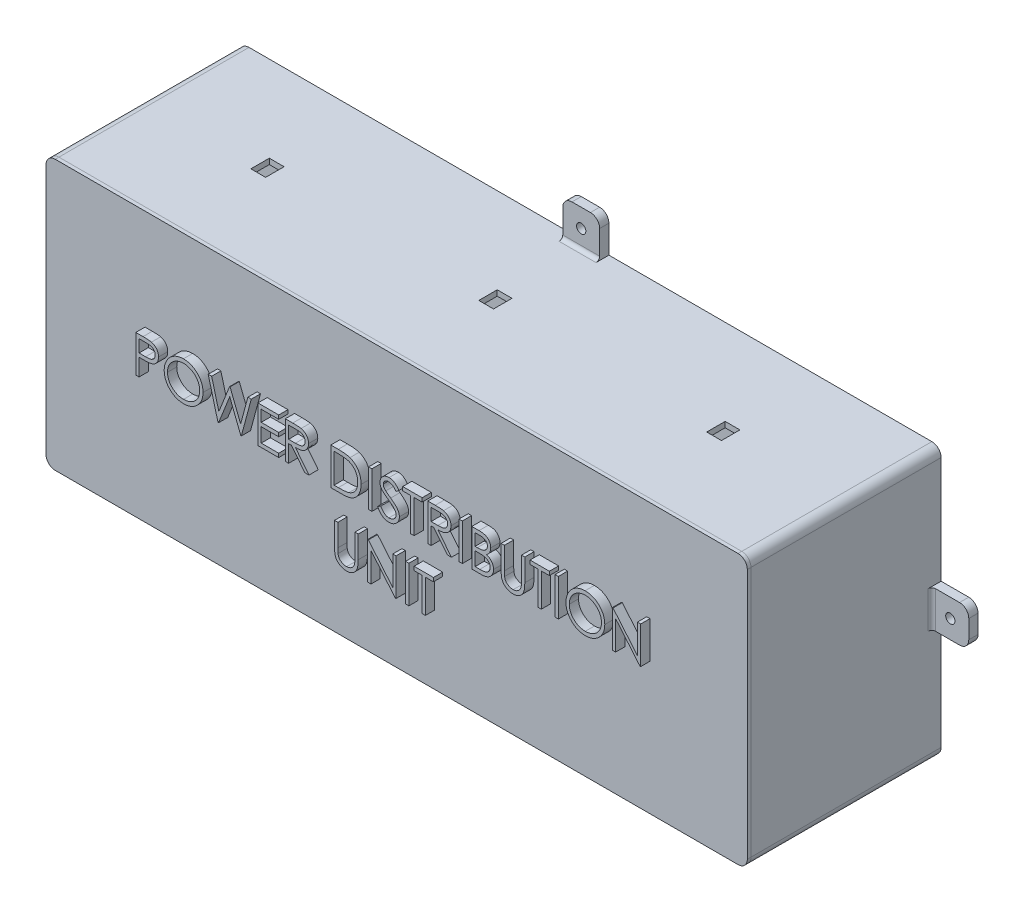
SolidWorks part; units mm, degrees
ref_plane "Front Plane" through (0, 0, 0) normal (0, 0, 1) x (1, 0, 0)
ref_plane "Top Plane" through (0, 0, 0) normal (0, 1, 0) x (1, 0, 0)
ref_plane "Right Plane" through (0, 0, 0) normal (1, 0, 0) x (0, 0, -1)
sketch "Sketch1" plane through (0, 0, 0) normal (0, 0, 1) x (1, 0, 0)
  line L0 (-190, 73) -> (190, 73)
  line L1 (-187, -70) -> (187, -70)
  line L2 (-187, -70) -> (-187, 70)
  line L3 (-187, 70) -> (187, 70)
  line L4 (187, -70) -> (187, 70)
  line L5 (0, 70) -> (0, -70) construction
  line L6 (-187, 0) -> (187, 0) construction
  line L7 (190, -73) -> (190, 73)
  line L8 (-190, -73) -> (190, -73)
  line L9 (-190, -73) -> (-190, 73)
  point P0 (0, 0)
  dimension "D1" = 140
  dimension "D2" = 380
  dimension "D3" = 3
extrude "Boss-Extrude1" add sketch "Sketch1" along normal blind 100
sketch "Sketch2" plane through (0, 0, 0) normal (0, 0, -1) x (-1, 0, 0)
  line L0 (-190, -73) -> (-190, 73) construction
  line L1 (190, -73) -> (-190, -73) construction
  line L2 (190, 73) -> (190, -73) construction
  line L3 (-190, 73) -> (190, 73) construction
  line L4 (-190, -73) -> (-190, 73)
  line L5 (190, -73) -> (-190, -73)
  line L6 (190, 73) -> (190, -73)
  line L7 (-190, 73) -> (190, 73)
extrude "Boss-Extrude2" add sketch "Sketch2" along normal blind 3
ref_plane "Plane1" through (0, 0, 5) normal (0, 0, 1) x (1, 0, 0)
sketch "Sketch3" plane through (0, 0, 5) normal (0, 0, 1) x (1, 0, 0)
  line L0 (-177, 60) -> (-177, -60)
  line L1 (-177, -60) -> (177, -60)
  line L2 (177, -60) -> (177, 60)
  line L3 (177, 60) -> (-177, 60)
  line L4 (-187, 70) -> (-187, -70)
  line L5 (-187, -70) -> (187, -70)
  line L6 (187, -70) -> (187, 70)
  line L7 (187, 70) -> (-187, 70)
  line L8 (-187, 70) -> (-187, -70)
  line L9 (-187, -70) -> (187, -70)
  line L10 (187, -70) -> (187, 70)
  line L11 (187, 70) -> (-187, 70)
  dimension "D1" = 0
  dimension "D2" = 10
extrude "Boss-Extrude3" add sketch "Sketch3" along normal blind 3 separate body contours L2 L3 L0 L1 region at (0, 0, 5)
sketch "Sketch4" plane through (0, 70, 0) normal (0, -1, 0) x (1, 0, 0)
  line L1 (190, 48.5) -> (-190, 48.5) construction
  line L2 (190, 100) -> (190, -3) construction
  line L3 (-190, 100) -> (-190, -3) construction
  line L15 (127.5, 43.5) -> (119.5, 43.5)
  line L16 (127.5, 43.5) -> (127.5, 53.5)
  line L21 (127.5, 53.5) -> (119.5, 53.5)
  line L22 (119.5, 43.5) -> (119.5, 53.5)
  line L27 (123.5, 53.5) -> (123.5, 43.5) construction
  line L28 (127.5, 48.5) -> (119.5, 48.5) construction
  line L30 (-127.5, 43.5) -> (-119.5, 43.5)
  line L31 (-127.5, 43.5) -> (-127.5, 53.5)
  line L32 (-127.5, 53.5) -> (-119.5, 53.5)
  line L33 (-119.5, 43.5) -> (-119.5, 53.5)
  line L34 (-123.5, 53.5) -> (-123.5, 43.5) construction
  line L35 (-127.5, 48.5) -> (-119.5, 48.5) construction
  line L36 (4, 43.5) -> (-4, 43.5)
  line L37 (4, 43.5) -> (4, 53.5)
  line L38 (4, 53.5) -> (-4, 53.5)
  line L39 (-4, 43.5) -> (-4, 53.5)
  line L40 (0, 53.5) -> (0, 43.5) construction
  line L41 (4, 48.5) -> (-4, 48.5) construction
  point P6 (123.5, 48.5)
  point P7 (-123.5, 48.5)
  point P8 (123.5, 48.5)
  point P12 (-123.5, 48.5)
  point P16 (0, 48.5)
  point P17 (0, 48.5)
  dimension "D5" = 8
  dimension "D6" = 10
  dimension "D7" = 10
  dimension "D1" = 380
  dimension "D2" = 66.5
  dimension "D3" = 66.5
  dimension "D4" = 190
  dimension "D8" = 8
  dimension "D9" = 8
  dimension "D10" = 10
extrude "Cut-Extrude1" cut sketch "Sketch4" against normal up to surface (3 mm away) contours L22 L15 L16 L21 | L39 L36 L37 L38 | L31 L32 L33 L30 region at (123.5, 70, 48.5) region at (0, 70, 48.5) up to face at (0, 73, 48.5)
sketch "Sketch6" plane through (-190, 0, 0) normal (-1, 0, 0) x (0, 0, 1)
  line L0 (48.5, 73) -> (48.5, -73) construction
  line L5 (100, 73) -> (100, -73) construction
  line L6 (43.5, -28.6) -> (53.5, -28.6)
  line L7 (43.5, -33.8) -> (53.5, -33.8)
  line L8 (43.5, -33.8) -> (43.5, -41.8)
  line L9 (43.5, -41.8) -> (53.5, -41.8)
  line L10 (53.5, -33.8) -> (53.5, -41.8)
  line L11 (48.5, -41.8) -> (48.5, -33.8) construction
  line L12 (43.5, -37.8) -> (53.5, -37.8) construction
  line L17 (43.5, -28.6) -> (43.5, -36.6)
  line L18 (56, 2.6) -> (41, 2.6) construction
  line L19 (56, 37.8) -> (41, 37.8) construction
  line L20 (48.5, 45.3) -> (48.5, 30.3) construction
  line L21 (43.5, -36.6) -> (53.5, -36.6)
  line L22 (-3, -73) -> (-3, 73) construction
  line L23 (100, 73) -> (-3, 73) construction
  line L24 (53.5, -28.6) -> (53.5, -36.6)
  line L25 (100, -73) -> (-3, -73) construction
  line L26 (48.5, -36.6) -> (48.5, -28.6) construction
  line L30 (43.5, -32.6) -> (53.5, -32.6) construction
  circle A0 centre (48.5, 37.8) radius 7.5
  circle A1 centre (48.5, 2.6) radius 7.5
  point P2 (48.5, -32.6)
  point P6 (48.5, -37.8)
  point P12 (48.5, 2.6)
  dimension "D8" = 15
  dimension "D6" = 15
  dimension "D1" = 35.2
  dimension "D2" = 8
  dimension "D3" = 10
  dimension "D4" = 35.2
  dimension "D5" = 10
  dimension "D7" = 35.2
  dimension "D9" = 35.2
  dimension "D10" = 8
  dimension "D11" = 51.5
  dimension "D12" = 51.5
extrude "Cut-Extrude2" cut sketch "Sketch6" against normal up to surface (3 mm away) contours A1 | L8 L21 L10 L7 | L24 L6 L17 L7 | A0 region at (-190, -31.2, 48.5) region at (-190, -35.2, 48.5) region at (-190, 37.8, 48.5) region at (-190, 2.6, 48.5) up to face at (-187, 0, 50)
sketch "Sketch7" plane through (0, -73, 0) normal (0, -1, 0) x (1, 0, 0)
  line L0 (0, 22) -> (0, 12) construction
  line L1 (-5, 17) -> (5, 17) construction
  line L4 (190, -3) -> (-190, -3) construction
  circle A0 centre (0, 17) radius 5
  dimension "D2" = 10
  dimension "D3" = 0
  dimension "D5" = 20
extrude "Cut-Extrude3" cut sketch "Sketch7" against normal up to surface (3 mm away) up to face at (0, -70, 50)
fillet "Fillet1" radius 5 4 edges at (190, 73, 48.5) (190, -73, 48.5) (-190, 73, 48.5) (-190, -73, 48.5)
fillet "Fillet2" radius 5 4 edges at (187, 70, 50) (-187, 70, 50) (187, -70, 50) (-187, -70, 50)
sketch "Sketch8" plane through (-187, 0, 0) normal (1, 0, 0) x (0, 0, -1)
  line L0 (0, 65) -> (-100, 65) construction
  line L1 (-97, -22.5) -> (-94, -22.5)
  line L2 (-97, -22.5) -> (-97, -7.5)
  line L3 (-97, -7.5) -> (-94, -7.5)
  line L4 (-94, -22.5) -> (-94, -7.5)
  line L5 (-95.5, -7.5) -> (-95.5, -22.5) construction
  line L6 (-97, -15) -> (-94, -15) construction
  line L7 (-100, 65) -> (-100, -65) construction
  line L8 (-100, -65) -> (0, -65) construction
  point P0 (-95.5, -15)
  dimension "D1" = 3
  dimension "D2" = 15
  dimension "D3" = 80
  dimension "D4" = 3
  dimension "D5" = 50
extrude "Boss-Extrude4" add sketch "Sketch8" along normal blind 15
sketch "Sketch9" plane through (0, 70, 0) normal (0, -1, 0) x (1, 0, 0)
  line L0 (182, 0) -> (182, 100) construction
  line L1 (74.5, 94) -> (89.5, 94)
  line L2 (74.5, 94) -> (74.5, 97)
  line L3 (74.5, 97) -> (89.5, 97)
  line L4 (89.5, 94) -> (89.5, 97)
  line L5 (82, 97) -> (82, 94) construction
  line L6 (74.5, 95.5) -> (89.5, 95.5) construction
  line L7 (182, 100) -> (-182, 100) construction
  line L8 (-182, 100) -> (-182, 0) construction
  line L9 (-89.5, 94) -> (-74.5, 94)
  line L10 (-89.5, 94) -> (-89.5, 97)
  line L11 (-89.5, 97) -> (-74.5, 97)
  line L12 (-74.5, 94) -> (-74.5, 97)
  line L13 (-82, 97) -> (-82, 94) construction
  line L14 (-89.5, 95.5) -> (-74.5, 95.5) construction
  point P0 (82, 95.5)
  point P8 (-82, 95.5)
  dimension "D1" = 15
  dimension "D2" = 3
  dimension "D3" = 100
  dimension "D4" = 3
  dimension "D5" = 100
  dimension "D6" = 3
  dimension "D7" = 3
  dimension "D8" = 164
  dimension "D9" = 15
extrude "Boss-Extrude5" add sketch "Sketch9" along normal blind 15
ref_plane "Plane2" through (0, 0, 0) normal (0, -1, 0) x (-1, 0, 0)
ref_plane "Plane3" through (0, 0, 0) normal (1, 0, 0) x (0, 0, -1)
mirror "Mirror1" about plane through (0, 0, 0) normal (1, 0, 0) of "Boss-Extrude4"
mirror "Mirror2" about plane through (0, 0, 0) normal (0, -1, 0) of "Boss-Extrude5"
fillet "Fillet3" radius 3 12 edges at (89.5, -55, 95.5) (74.5, -55, 95.5) (172, -7.5, 95.5) (172, -22.5, 95.5) (74.5, 55, 95.5) (89.5, 55, 95.5) (-172, -7.5, 95.5) (-172, -22.5, 95.5) (-74.5, -55, 95.5) (-89.5, -55, 95.5) (-74.5, 55, 95.5) (-89.5, 55, 95.5)
sketch "Sketch10" plane through (0, 0, -3) normal (0, 0, -1) x (-1, 0, 0)
  line L0 (-185, 73) -> (185, 73) construction
  line L1 (-10, 73) -> (10, 73)
  line L2 (-10, 73) -> (-10, 88)
  line L3 (-5, 93) -> (5, 93)
  line L4 (10, 73) -> (10, 88)
  line L5 (-2.5, 83) -> (2.5, 83) construction
  line L6 (0, 85.5) -> (0, 80.5) construction
  line L7 (0, 80.5) -> (0, 0) construction
  circle A0 centre (0, 83) radius 2.5
  arc A1 (5, 93) -> (10, 88) centre (5, 88) cw
  arc A2 (-10, 88) -> (-5, 93) centre (-5, 88) cw
  dimension "D1" = 5
  dimension "D6" = 5
  dimension "D2" = 10
  dimension "D3" = 10
  dimension "D4" = 10
  dimension "D5" = 10
extrude "Boss-Extrude6" add sketch "Sketch10" against normal blind 5
mirror "Mirror3" about plane through (0, 0, 0) normal (0, -1, 0) of "Boss-Extrude6"
sketch "Sketch11" plane through (0, 0, 0) normal (0, 0, 1) x (1, 0, 0)
  line L0 (15, 52) -> (15, 60) construction
  line L1 (23, 60) -> (-177, 60) construction
  line L2 (15, 52) -> (23, 52) construction
  line L3 (23, -90) -> (23, 60) construction
  line L4 (-167, 50) -> (-167, 60) construction
  line L5 (-167, 50) -> (-177, 50) construction
  line L6 (-177, 60) -> (-177, -90) construction
  line L7 (-167, -80) -> (-177, -80) construction
  line L8 (-167, -80) -> (-167, -90) construction
  line L9 (-177, -90) -> (23, -90) construction
  line L12 (23, -85) -> (26, -85)
  line L13 (26, -85) -> (26, -93)
  line L14 (26, -93) -> (18, -93)
  line L15 (18, -93) -> (18, -90)
  line L16 (23, -85) -> (18, -85)
  line L17 (18, -85) -> (18, -90)
  line L18 (-63.4828, 60) -> (-63.4828, 55)
  line L19 (-63.4828, 55) -> (-33.4828, 55)
  line L20 (-33.4828, 55) -> (-33.4828, 60)
  line L22 (-63.4828, 60) -> (-63.4828, 63)
  line L23 (-63.4828, 63) -> (-33.4828, 63)
  line L24 (-33.4828, 63) -> (-33.4828, 60)
  line L33 (-62.623, -70) -> (-33.4828, -70)
  line L34 (-62.623, -70) -> (-62.623, -78)
  line L35 (-62.623, -78) -> (-33.4828, -78)
  line L36 (-33.4828, -70) -> (-33.4828, -78)
  circle A0 centre (15, 52) radius 4
  circle A1 centre (15, 52) radius 1.75
  circle A2 centre (-167, 50) radius 4
  circle A3 centre (-167, 50) radius 1.75
  circle A4 centre (-167, -80) radius 4
  circle A5 centre (-167, -80) radius 1.75
  point P3 (19, 52)
  dimension "D1" = 8
  dimension "D2" = 3.5
  dimension "D6" = 8
  dimension "D7" = 3.5
  dimension "D10" = 3.5
  dimension "D11" = 8
  dimension "D3" = 8
  dimension "D4" = 8
  dimension "D5" = 4
  dimension "D8" = 10
  dimension "D9" = 10
  dimension "D12" = 10
  dimension "D13" = 10
  dimension "D14" = 3
  dimension "D15" = 3
  dimension "D16" = 5
  dimension "D17" = 5
  dimension "D18" = 3
  dimension "D20" = 5
extrude "Boss-Extrude7" add sketch "Sketch11" along normal blind 15
ref_plane "Plane4" through (-77, 0, 0) normal (1, 0, 0) x (0, 0, -1)
sketch "Sketch12" plane through (0, 0, 15) normal (0, 0, 1) x (1, 0, 0)
  line L0 (18, -93) -> (26, -93)
  line L1 (26, -93) -> (26, -85)
  line L2 (26, -85) -> (23, -85)
  line L3 (26, -85) -> (18, -85) construction
  line L4 (23, -85) -> (23, -90)
  line L5 (23, -90) -> (18, -90)
  line L6 (18, -85) -> (18, -93) construction
  line L7 (-177, -90) -> (23, -90) construction
  line L8 (18, -90) -> (18, -93)
extrude "Boss-Extrude8" add sketch "Sketch12" along normal blind 5
sketch "Sketch13" plane through (0, 0, 15) normal (0, 0, 1) x (1, 0, 0)
  line L0 (-33.4828, 55) -> (-33.4828, 63) construction
  line L1 (-63.4828, 63) -> (-33.4828, 63)
  line L2 (-63.4828, 63) -> (-63.4828, 60)
  line L3 (-63.4828, 60) -> (-33.4828, 60)
  line L4 (-33.4828, 63) -> (-33.4828, 60)
  line L5 (23, 60) -> (-177, 60) construction
  line L6 (-33.4828, -78) -> (-33.4828, -73) construction
  line L7 (-62.623, -78) -> (-33.4828, -78)
  line L8 (-62.623, -78) -> (-62.623, -90)
  line L9 (-62.623, -90) -> (-33.4828, -90)
  line L10 (-33.4828, -78) -> (-33.4828, -90)
  line L11 (-177, -90) -> (23, -90) construction
extrude "Boss-Extrude9" add sketch "Sketch13" along normal blind 5
sketch "Sketch14" plane through (0, 0, -3) normal (0, 0, -1) x (-1, 0, 0)
  line L0 (-190, 0) -> (-213.8528, 0) construction
  line L1 (-190, -68) -> (-190, 68) construction
  line L3 (-205, -10) -> (-190, -10)
  line L4 (-210, -5) -> (-210, 5)
  line L5 (-205, 10) -> (-190, 10)
  line L6 (-190, -10) -> (-190, 10)
  circle A0 centre (-200, 0) radius 2.5
  arc A1 (-210, 5) -> (-205, 10) centre (-205, 5) cw
  arc A2 (-205, -10) -> (-210, -5) centre (-205, -5) cw
  point P14 (-210, -10)
  dimension "D1" = 5
  dimension "D6" = 5
  dimension "D2" = 10
  dimension "D3" = 10
  dimension "D4" = 10
  dimension "D5" = 20
extrude "Boss-Extrude10" add sketch "Sketch14" against normal blind 5
mirror "Mirror4" about plane through (0, 0, 0) normal (1, 0, 0) of "Boss-Extrude10"
fillet "Fillet5" radius 2 4 edges at (0, -73, 2) (-190, 0, 2) (0, 73, 2) (190, 0, 2)
sketch "Sketch15" plane through (0, 0, 100) normal (0, 0, 1) x (1, 0, 0)
  line L4 (190, -68) -> (190, 68)
  line L5 (185, 73) -> (-185, 73)
  line L6 (-190, 68) -> (-190, -68)
  line L7 (-185, -73) -> (185, -73)
  line L8 (190, -68) -> (190, 68)
  line L9 (185, 73) -> (-185, 73)
  line L10 (-190, 68) -> (-190, -68)
  line L11 (-185, -73) -> (185, -73)
  arc A4 (190, 68) -> (185, 73) centre (185, 68) ccw
  arc A5 (-185, 73) -> (-190, 68) centre (-185, 68) ccw
  arc A6 (-190, -68) -> (-185, -73) centre (-185, -68) ccw
  arc A7 (185, -73) -> (190, -68) centre (185, -68) ccw
  arc A8 (190, 68) -> (185, 73) centre (185, 68) ccw
  arc A9 (-185, 73) -> (-190, 68) centre (-185, 68) ccw
  arc A10 (-190, -68) -> (-185, -73) centre (-185, -68) ccw
  arc A11 (185, -73) -> (190, -68) centre (185, -68) ccw
  dimension "D1" = 0
extrude "Boss-Extrude11" add sketch "Sketch15" along normal blind 2 separate body
sketch "Sketch16" plane through (0, 0, 102) normal (0, 0, 1) x (1, 0, 0)
  text T0 "POWER DISTRIBUTION \r\n              UNIT" font "Century Gothic" height 20
extrude "Boss-Extrude12" add sketch "Sketch16" along normal blind 5
